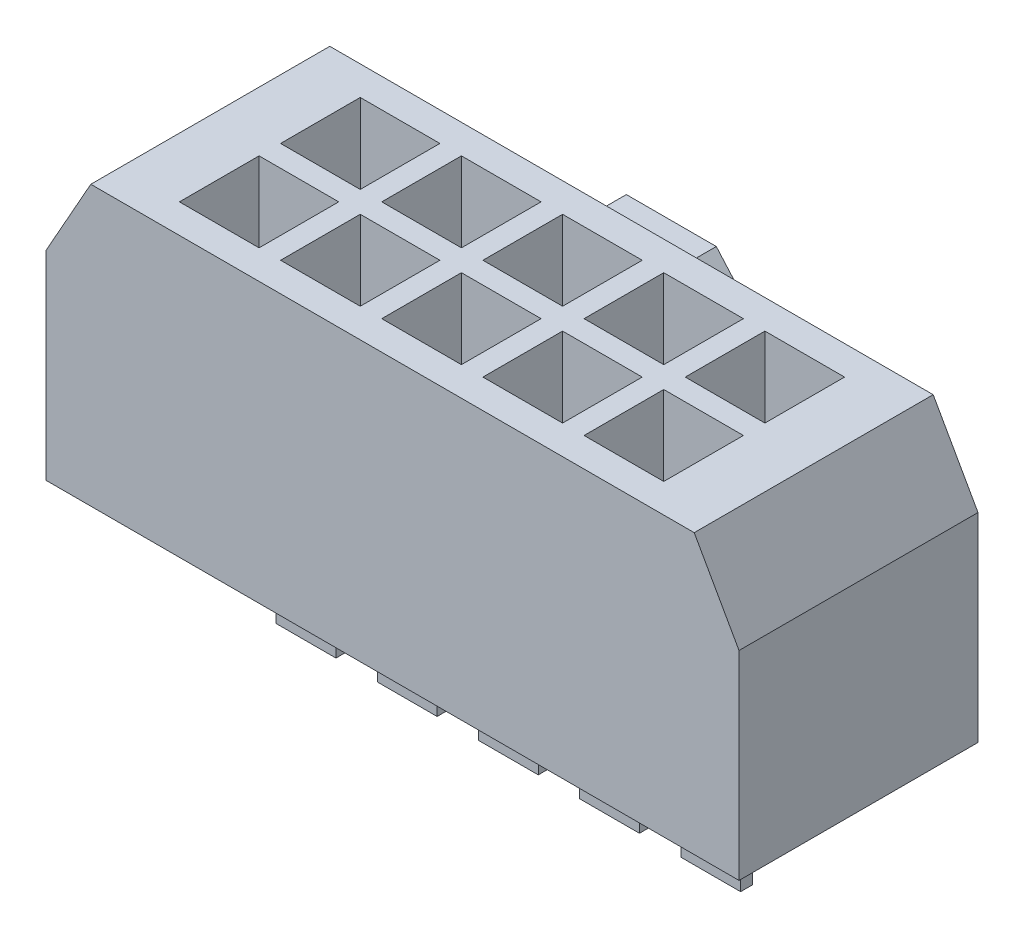
SolidWorks part; units mm, degrees
ref_plane "Front" through (0, 0, 0) normal (0, 0, 1) x (1, 0, 0)
ref_plane "Top" through (0, 0, 0) normal (0, 1, 0) x (1, 0, 0)
ref_plane "Right" through (0, 0, 0) normal (1, 0, 0) x (0, 0, -1)
sketch "Эскиз1" plane through (0, 0, 0) normal (0, 0, 1) x (1, 0, 0)
  line L0 (0, 5.8423) -> (0, -4.6539) construction
  line L1 (-9.0888, 0) -> (10.6015, 0) construction
  line L2 (-8.7, -3.5) -> (8.7, -3.5)
  line L3 (-8.7, -3.5) -> (-8.7, 3.5) construction
  line L4 (-8.7, -3.5) -> (-8.7, 1.5)
  line L5 (-8.7, 1.5) -> (-7.575, 3.5)
  line L6 (-7.575, 3.5) -> (7.575, 3.5)
  line L7 (8.7, -3.5) -> (8.7, 1.5)
  line L8 (8.7, 1.5) -> (7.575, 3.5)
  line L9 (-1.9, -3.5) -> (-1.9, 2.1221)
  line L10 (-1.9, 2.1221) -> (-1.1294, 2.999)
  line L11 (-1.1294, 2.999) -> (1.1294, 2.999)
  line L12 (1.9, 2.1221) -> (1.1294, 2.999)
  line L13 (1.9, -3.5) -> (1.9, 2.1221)
  point P5 (0, -3.5)
  point P6 (-8.7, 0)
  point P17 (0, 3.5)
  point P19 (0, 0)
  point P21 (0, 2.999)
  dimension "D1" = 17.4
  dimension "D2" = 7
  dimension "D3" = 1.125
  dimension "D4" = 5
  dimension "D5" = 1.9
extrude "Бобышка-Вытянуть1" add sketch "Эскиз1" along normal mid plane 6 contours L13 L2 L7 L8 L6 L5 L4 L9 L10 L11 L12 | L2 L13 L12 L11 L10 L9 region at (-8.5124, -1, 0) region at (0, -0.3337, 0)
extrude "Бобышка-Вытянуть2" add sketch "Эскиз1<3>" against normal blind 1 from surface contours L2 L13 L12 L11 L10 L9 region at (0, -0.3337, 0) starting at face at (0, 0.5, -3)
sketch "Эскиз1<3>" plane through (0, 0, 0) normal (0, 0, 1) x (1, 0, 0) same geometry as "Эскиз1"
sketch "Эскиз2" plane through (0, 3.5, 0) normal (0, 1, 0) x (1, 0, 0)
  line L0 (-7.3042, 0) -> (8.5138, 0) construction
  line L1 (0, 4.9009) -> (0, -4.5922) construction
  line L2 (-1, 2.27) -> (1, 2.27)
  line L3 (-1, 2.27) -> (-1, 0.27)
  line L4 (-1, 0.27) -> (1, 0.27)
  line L5 (1, 2.27) -> (1, 0.27)
  line L6 (-7.3042, 1.27) -> (8.4447, 1.27) construction
  line L8 (-1, -0.27) -> (1, -0.27)
  line L9 (1, -2.27) -> (1, -0.27)
  line L10 (-1, -2.27) -> (1, -2.27)
  line L11 (-1, -2.27) -> (-1, -0.27)
  line L12 (1.54, 2.27) -> (3.54, 2.27)
  line L13 (1.54, 2.27) -> (1.54, 0.27)
  line L14 (1.54, 0.27) -> (3.54, 0.27)
  line L15 (3.54, 2.27) -> (3.54, 0.27)
  line L16 (1.54, -0.27) -> (3.54, -0.27)
  line L17 (3.54, -2.27) -> (3.54, -0.27)
  line L18 (1.54, -2.27) -> (3.54, -2.27)
  line L19 (1.54, -2.27) -> (1.54, -0.27)
  line L20 (-3.54, 2.27) -> (-1.54, 2.27)
  line L21 (-3.54, 2.27) -> (-3.54, 0.27)
  line L22 (-3.54, 0.27) -> (-1.54, 0.27)
  line L23 (-1.54, 2.27) -> (-1.54, 0.27)
  line L24 (-3.54, -0.27) -> (-1.54, -0.27)
  line L25 (-1.54, -2.27) -> (-1.54, -0.27)
  line L26 (-3.54, -2.27) -> (-1.54, -2.27)
  line L27 (-3.54, -2.27) -> (-3.54, -0.27)
  line L28 (-6.08, 2.27) -> (-4.08, 2.27)
  line L29 (-6.08, 2.27) -> (-6.08, 0.27)
  line L30 (-6.08, 0.27) -> (-4.08, 0.27)
  line L31 (-4.08, 2.27) -> (-4.08, 0.27)
  line L32 (-6.08, -0.27) -> (-4.08, -0.27)
  line L33 (-4.08, -2.27) -> (-4.08, -0.27)
  line L34 (-6.08, -2.27) -> (-4.08, -2.27)
  line L35 (-6.08, -2.27) -> (-6.08, -0.27)
  line L36 (4.08, 2.27) -> (6.08, 2.27)
  line L37 (4.08, 2.27) -> (4.08, 0.27)
  line L38 (4.08, 0.27) -> (6.08, 0.27)
  line L39 (6.08, 2.27) -> (6.08, 0.27)
  line L40 (4.08, -0.27) -> (6.08, -0.27)
  line L41 (6.08, -2.27) -> (6.08, -0.27)
  line L42 (4.08, -2.27) -> (6.08, -2.27)
  line L43 (4.08, -2.27) -> (4.08, -0.27)
  point P9 (0, 2.27)
  point P12 (-1, 1.27)
  dimension "D1" = 2
  dimension "D2" = 2
  dimension "D3" = 1.27
  dimension "D4" = 2
extrude "Вырез-Вытянуть1" cut sketch "Эскиз2" against normal blind 3
sketch "Эскиз3" plane through (0, -3.5, 0) normal (0, -1, 0) x (1, 0, 0)
  line L0 (-7.0277, 0) -> (7.9608, 0) construction
  line L1 (0, 4.0853) -> (0, -4.7166) construction
  line L2 (-0.115, 0.725) -> (1.385, 0.725)
  line L3 (-0.115, 0.725) -> (-0.115, 0.425)
  line L4 (-0.115, 0.425) -> (1.385, 0.425)
  line L5 (1.385, 0.725) -> (1.385, 0.425)
  line L6 (-1.385, -0.425) -> (0.115, -0.425)
  line L7 (-1.385, -0.425) -> (-1.385, -0.725)
  line L8 (-1.385, -0.725) -> (0.115, -0.725)
  line L9 (0.115, -0.425) -> (0.115, -0.725)
  line L10 (2.425, 0.725) -> (3.925, 0.725)
  line L11 (2.425, 0.725) -> (2.425, 0.425)
  line L12 (2.425, 0.425) -> (3.925, 0.425)
  line L13 (3.925, 0.725) -> (3.925, 0.425)
  line L14 (1.155, -0.425) -> (2.655, -0.425)
  line L15 (1.155, -0.425) -> (1.155, -0.725)
  line L16 (1.155, -0.725) -> (2.655, -0.725)
  line L17 (2.655, -0.425) -> (2.655, -0.725)
  line L18 (-2.655, 0.725) -> (-1.155, 0.725)
  line L19 (-2.655, 0.725) -> (-2.655, 0.425)
  line L20 (-2.655, 0.425) -> (-1.155, 0.425)
  line L21 (-1.155, 0.725) -> (-1.155, 0.425)
  line L22 (-3.925, -0.425) -> (-2.425, -0.425)
  line L23 (-3.925, -0.425) -> (-3.925, -0.725)
  line L24 (-3.925, -0.725) -> (-2.425, -0.725)
  line L25 (-2.425, -0.425) -> (-2.425, -0.725)
  line L26 (-1.385, -0.425) -> (-1.385, -0.725)
  line L27 (-3.925, -0.425) -> (-3.925, -0.725)
  line L28 (-5.195, 0.725) -> (-3.695, 0.725)
  line L29 (-5.195, 0.725) -> (-5.195, 0.425)
  line L30 (-5.195, 0.425) -> (-3.695, 0.425)
  line L31 (-3.695, 0.725) -> (-3.695, 0.425)
  line L32 (-6.465, -0.425) -> (-4.965, -0.425)
  line L33 (-6.465, -0.425) -> (-6.465, -0.725)
  line L34 (-6.465, -0.725) -> (-4.965, -0.725)
  line L35 (-4.965, -0.425) -> (-4.965, -0.725)
  line L36 (-3.925, -0.425) -> (-3.925, -0.725)
  line L37 (4.965, 0.725) -> (6.465, 0.725)
  line L38 (4.965, 0.725) -> (4.965, 0.425)
  line L39 (4.965, 0.425) -> (6.465, 0.425)
  line L40 (6.465, 0.725) -> (6.465, 0.425)
  line L41 (3.695, -0.425) -> (5.195, -0.425)
  line L42 (3.695, -0.425) -> (3.695, -0.725)
  line L43 (3.695, -0.725) -> (5.195, -0.725)
  line L44 (5.195, -0.425) -> (5.195, -0.725)
  point P9 (1.385, 0.575)
  point P14 (0.115, -0.575)
  point P17 (-0.635, -0.725)
  point P18 (0.635, 0.425)
  point P19 (0.635, 0.725)
  dimension "D1" = 1.5
  dimension "D2" = 0.3
  dimension "D3" = 0.575
  dimension "D4" = 1.15
  dimension "D5" = 1.27
  dimension "D6" = 0.635
  dimension "D7" = 2
  dimension "D8" = 2
  dimension "D9" = 2
extrude "Бобышка-Вытянуть3" add sketch "Эскиз3" along normal blind 2.5 from surface contours L25 L22 L23 L24 | L21 L18 L19 L20 | L9 L6 L7 L8 | L5 L2 L3 L4 | L17 L14 L15 L16 | L13 L10 L11 L12 | L28 L31 L30 L29 | L32 L35 L34 L33 | L37 L40 L39 L38 | L41 L44 L43 L42 region at (0.635, -3.5, 0.575) region at (-0.635, -3.5, -0.575) region at (3.175, -3.5, 0.575) region at (1.905, -3.5, -0.575) region at (-1.905, -3.5, 0.575) region at (-3.175, -3.5, -0.575) starting at face at (0, -3.5, -1.75)
